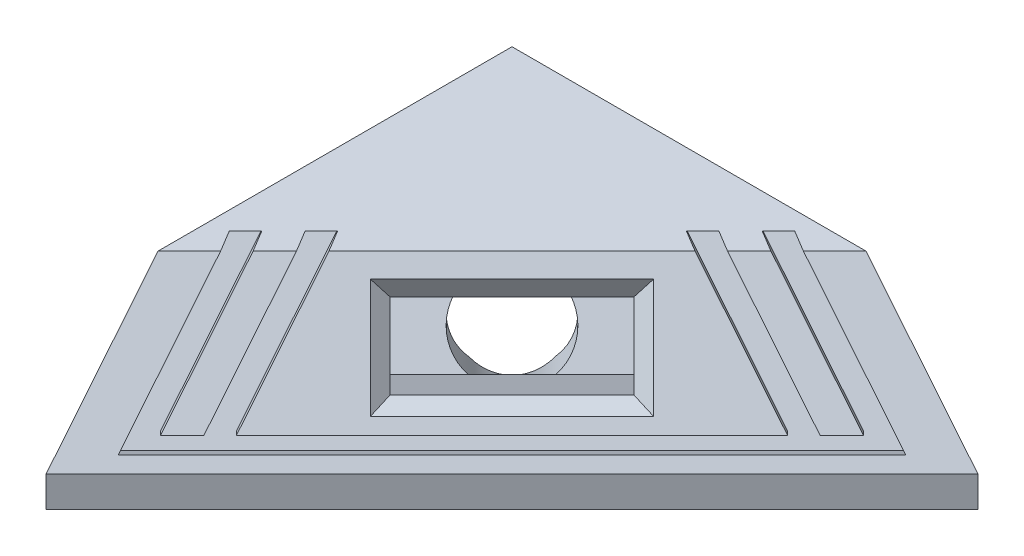
SolidWorks part; units mm, degrees
ref_plane "Front Plane" through (0, 0, 0) normal (0, 0, 1) x (1, 0, 0)
ref_plane "Top Plane" through (0, 0, 0) normal (0, 1, 0) x (1, 0, 0)
ref_plane "Right Plane" through (0, 0, 0) normal (1, 0, 0) x (0, 0, -1)
sketch "Sketch1" plane through (0, 0, 0) normal (0, 1, 0) x (1, 0, 0)
  line L0 (0, 0) -> (0, -34)
  line L1 (0, -55) -> (0, 55) construction
  line L2 (0, -34) -> (34, 0)
  line L3 (-55, 0) -> (55, 0) construction
  line L4 (34, 0) -> (0, 0)
  dimension "D1" = 34
extrude "Boss-Extrude1" add sketch "Sketch1" along normal blind 18
sketch "Sketch3" plane through (17, 0, 17) normal (0.7071, 0, 0.7071) x (0.7071, 0, -0.7071)
  line L0 (-24.0416, 7.9909) -> (24.0416, 7.9909)
  line L1 (-24.0416, 18) -> (-24.0416, 0) construction
  line L2 (24.0416, 18) -> (24.0416, 0) construction
ref_plane "Plane2" through (15.1967, 12.4081, 15.1967) normal (0.6124, 0.5, 0.6124) x (0.7071, 0, -0.7071)
sketch "Sketch6" plane through (15.1967, 12.4081, 15.1967) normal (0.6124, 0.5, 0.6124) x (0.7071, 0, -0.7071)
  line L0 (-24.0416, -5.1005) -> (24.0416, -5.1005)
  line L1 (24.0416, -5.1005) -> (24.0416, 7.3663)
  line L2 (24.0416, 7.3663) -> (-24.0416, 7.3663)
  line L3 (-24.0416, 7.3663) -> (-24.0416, -5.1005)
  line L4 (0, 7.3663) -> (0, -1.1005) construction
  line L5 (-2.2489, -1.1005) -> (-6.3, -1.1005)
  line L6 (-6.3, 3.9995) -> (-2.2489, 3.9995)
  line L7 (-6.3, 3.9995) -> (-6.3, -1.1005)
  line L8 (2.2489, -1.1005) -> (6.3, -1.1005)
  line L9 (6.3, 3.9995) -> (6.3, -1.1005)
  line L10 (-6.3, 3.9995) -> (6.3, -1.1005) construction
  line L11 (-6.3, -1.1005) -> (6.3, 3.9995) construction
  line L12 (-15.1668, 8.4066) -> (-21.2132, -3.6863) construction
  line L13 (-18.1359, -3.1005) -> (-12.9025, 7.3663)
  line L14 (-18.1359, -3.1005) -> (-15.8999, -3.1005)
  line L15 (-20.313, -4.1005) -> (0, -4.1005)
  line L16 (-15.8999, -3.1005) -> (-10.6665, 7.3663)
  line L17 (-8.9894, 7.3663) -> (-14.2228, -3.1005)
  line L18 (-14.2228, -3.1005) -> (0, -3.1005)
  line L19 (-20.313, -4.1005) -> (-14.5796, 7.3663)
  line L20 (0, -3.1005) -> (0, -4.1005)
  line L21 (0, -1.1005) -> (0, -3.1005) construction
  line L22 (0, -1.1005) -> (0, -3.1005) construction
  line L23 (2.2489, 3.9995) -> (6.3, 3.9995)
  line L24 (0, -3.4189) -> (-1.5782, -3.4189) construction
  line L25 (-6.3, -1.7373) -> (6.3, -1.7373) construction
  line L26 (-2.2489, 3.9995) -> (0, 3.9995)
  line L27 (0, 3.9995) -> (2.2489, 3.9995)
  line L28 (-2.2489, -1.1005) -> (0, -1.1005)
  line L29 (0, -1.1005) -> (2.2489, -1.1005)
  circle A0 centre (0, 1.4495) radius 3.4
  point P4 (0, 1.4495)
  dimension "D9" = 6.8
  dimension "D1" = 12.6
  dimension "D2" = 5.1
  dimension "D3" = 1
  dimension "D4" = 1.5
  dimension "D5" = 1
  dimension "D6" = 2
  dimension "D7" = 1.5
  dimension "D8" = 2
extrude "Cut-Extrude2" cut sketch "Sketch6" along normal blind 9 contours L26 A0 L28 L29 L27 | L27 A0 L26 | L28 A0 L29 | A0 L6 L7 L5 | A0 L8 L9 L23 | L18 L20 L15 L19 L2 L3 L0 L1 L17 A0 L23 L9 L8 L5 L7 L6 | L20 L18 L17 L2 L16 L14 L13 L19 L15 | L14 L16 L2 L13 region at (-1.8526, 13.3892, 31.4449) region at (6.1204, 12.4489, 24.2397) region at (4.2594, 14.2552, 24.6258) region at (14.6842, 13.6634, 14.6842) region at (11.3916, 13.6634, 17.9768) region at (15.7074, 11.1572, 15.7074) region at (13.6611, 16.1696, 13.6611) region at (17.9768, 13.6634, 11.3916)
extrude "Cut-Extrude3" cut sketch "Sketch6<6>" against normal blind 12.5 and the other way through all contours L9 L6 L7 L8 | L26 A0 L28 L29 L27 | A0 L6 L7 L5 region at (14.6842, 13.6634, 14.6842) region at (11.3916, 13.6634, 17.9768) region at (17.9768, 13.6634, 11.3916)
sketch "Sketch6<6>" plane through (15.1967, 12.4081, 15.1967) normal (0.6124, 0.5, 0.6124) x (0.7071, 0, -0.7071) same geometry as "Sketch6"
extrude "Cut-Extrude4" cut sketch "Sketch6<8>" against normal blind 2.5 contours L20 L18 L17 L2 L16 L14 L13 L19 L15 region at (6.1204, 12.4489, 24.2397)
sketch "Sketch6<8>" plane through (15.1967, 12.4081, 15.1967) normal (0.6124, 0.5, 0.6124) x (0.7071, 0, -0.7071) same geometry as "Sketch6"
ref_plane "Plane3" through (0, 0, 0) normal (-0.7071, 0, 0.7071) x (0.3536, -0.866, 0.3536)
mirror "Mirror1" about plane through (0, 0, 0) normal (-0.7071, 0, 0.7071) of "Cut-Extrude4"
chamfer "Chamfer1" distance 10 angle 30 1 edges at (17, 0, 17) first distance on face at (11.3333, 0, 11.3333)
chamfer "Chamfer2" distance 1 angle 45 4 edges at (19.139, 13.6634, 10.2295) (15.5858, 11.455, 15.5858) (10.2295, 13.6634, 19.139) (13.7827, 15.8717, 13.7827)
extrude "Cut-Extrude5" cut sketch "Sketch6<9>" against normal through all from surface contours L27 A0 L26 | L26 A0 L28 L29 L27 | L28 A0 L29 region at (14.6842, 13.6634, 14.6842) region at (15.7074, 11.1572, 15.7074) region at (13.6611, 16.1696, 13.6611) starting at face at (7.0296, 7.4134, 7.0296)
sketch "Sketch6<9>" plane through (15.1967, 12.4081, 15.1967) normal (0.6124, 0.5, 0.6124) x (0.7071, 0, -0.7071) same geometry as "Sketch6"
